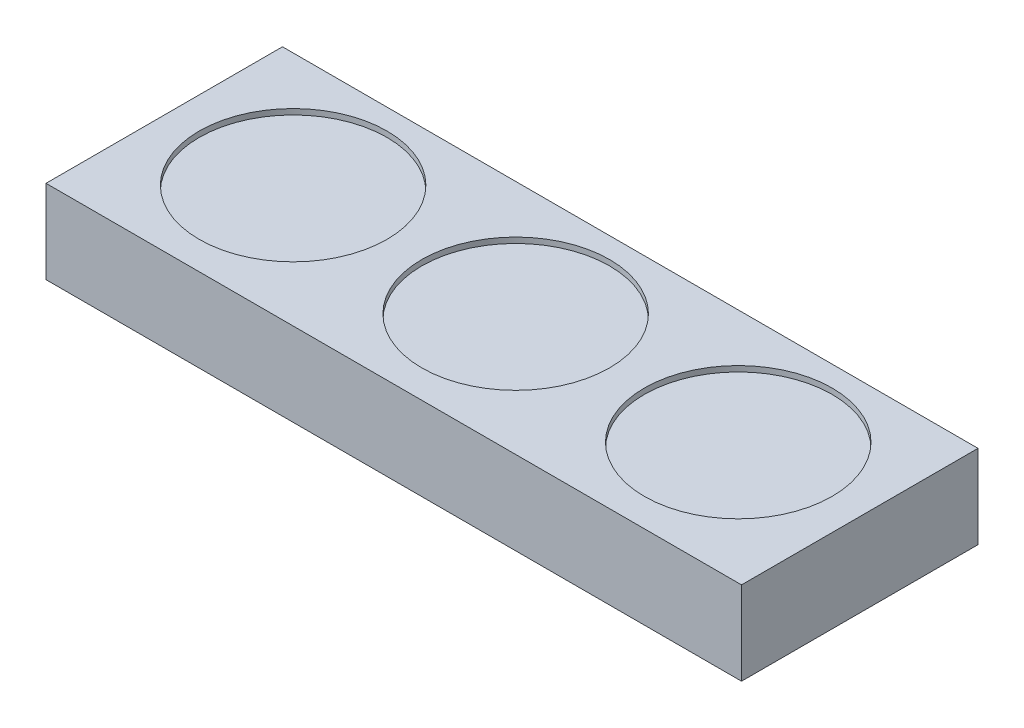
SolidWorks part; units mm, degrees
ref_plane "Front Plane" through (0, 0, 0) normal (0, 0, 1) x (1, 0, 0)
ref_plane "Top Plane" through (0, 0, 0) normal (0, 1, 0) x (1, 0, 0)
ref_plane "Right Plane" through (0, 0, 0) normal (1, 0, 0) x (0, 0, -1)
sketch "Sketch1" plane through (0, 0, 0) normal (0, 1, 0) x (1, 0, 0)
  line L1 (-255.5147, 108.4559) -> (244.4853, 108.4559)
  line L2 (-255.5147, 108.4559) -> (-255.5147, -61.5441)
  line L3 (-255.5147, -61.5441) -> (244.4853, -61.5441)
  line L4 (244.4853, 108.4559) -> (244.4853, -61.5441)
  dimension "D1" = 500
  dimension "D2" = 170
extrude "Boss-Extrude1" add sketch "Sketch1" along normal blind 60
sketch "Sketch3" plane through (0, 60, 0) normal (0, 1, 0) x (1, 0, 0)
  line L0 (244.4853, -61.5441) -> (244.4853, 108.4559) construction
  circle A0 centre (-5.5147, 26.0941) radius 67.5
  circle A1 centre (154.4853, 26.0941) radius 67.5
  circle A2 centre (-165.5147, 26.0941) radius 67.5
  dimension "D1" = 160
  dimension "D4" = 135
  dimension "D2" = 160
  dimension "D3" = 90
extrude "Cut-Extrude1" cut sketch "Sketch3" against normal blind 4
